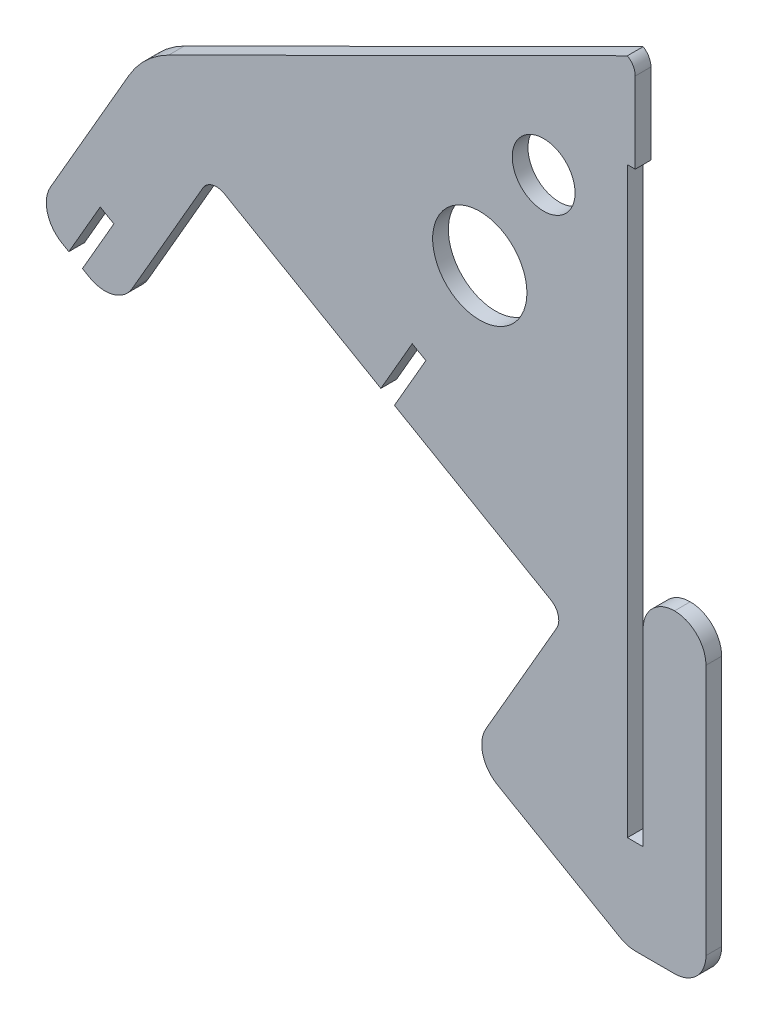
SolidWorks part; units mm, degrees
material "Oak"
ref_plane "Front Plane" through (0, 0, 0) normal (0, 0, 1) x (1, 0, 0)
ref_plane "Top Plane" through (0, 0, 0) normal (0, 1, 0) x (1, 0, 0)
ref_plane "Right Plane" through (0, 0, 0) normal (1, 0, 0) x (0, 0, -1)
sketch "Sketch1" plane through (0, 0, 0) normal (0, 0, 1) x (1, 0, 0)
  line L0 (19.8678, -317.9823) -> (-30.1322, -289.1148)
  line L1 (19.8678, -317.7572) -> (19.8678, -230.4572) construction
  line L2 (-30.1322, -289.1148) -> (-0.1322, -237.1533)
  line L3 (-0.1322, -237.1533) -> (-112.7155, -172.1533)
  line L4 (-112.7155, -172.1533) -> (-142.7155, -224.1148)
  line L5 (-142.7155, -224.1148) -> (-168.6963, -209.1148)
  line L6 (-168.6963, -209.1148) -> (-134.1825, -149.3352)
  line L7 (-134.1825, -149.3352) -> (19.8678, -72.5123)
  line L8 (19.8678, -130.2572) -> (19.8678, -42.9572) construction
  line L9 (19.8678, -72.5123) -> (19.8678, -287.9823)
  line L10 (19.8678, -317.9823) -> (44.8678, -317.9823)
  line L11 (44.8678, -317.9823) -> (44.8678, -217.9823)
  line L12 (44.8678, -217.9823) -> (24.8678, -217.9823)
  line L13 (24.8678, -217.9823) -> (24.8678, -287.9823)
  line L14 (24.8678, -317.7572) -> (24.8678, -230.4572) construction
  line L15 (24.8678, -287.9823) -> (19.8678, -287.9823)
  line L16 (24.8678, -230.4572) -> (24.8678, -130.2572) construction
  line L17 (-56.4239, -204.6533) -> (19.8678, -72.5123) construction
  line L18 (-58.589, -203.4033) -> (-48.589, -186.0828)
  line L19 (-48.589, -186.0828) -> (-44.2588, -188.5828)
  line L20 (-155.7059, -216.6148) -> (-145.7059, -199.2943) construction
  line L21 (-157.871, -215.3648) -> (-147.871, -198.0443)
  line L22 (-147.871, -198.0443) -> (-143.5409, -200.5443)
  line L23 (-153.5409, -217.8648) -> (-143.5409, -200.5443)
  line L24 (-54.2588, -205.9033) -> (-44.2588, -188.5828)
  line L25 (24.8678, -417.8572) -> (185.5376, -510.62) construction
  point P32 (-46.4239, -187.3328)
  dimension "D1" = 130
  dimension "D2" = 30
  dimension "D3" = 20
  dimension "D4" = 60
  dimension "D5" = 30
  dimension "D6" = 100
  dimension "D7" = 20
  dimension "D8" = 30
  dimension "D9" = 5
  dimension "D10" = 20
  dimension "D11" = 5
  dimension "D12" = 20
  dimension "D13" = 100
extrude "Boss-Extrude1" add sketch "Sketch1" along normal mid plane 5 contours L24 L3 L2 L0 L10 L11 L12 L13 L15 L9 L7 L6 L5 L21 L22 L23 L4 L18 L19 region at (-31.7791, -186.599, 0)
fillet "Fillet1" radius 10 7 edges at (-168.6963, -209.1148, 0) (-142.7155, -224.1148, 0) (-30.1322, -289.1148, 0) (19.8678, -317.9823, 0) (24.8678, -217.9823, 0) (44.8678, -217.9823, 0) (44.8678, -317.9823, 0)
sketch "Sketch2" plane through (0, 0, 2.5) normal (0, 0, 1) x (1, 0, 0)
  line L0 (19.8678, -72.5123) -> (22.3678, -72.5123)
  line L1 (22.3678, -72.5123) -> (22.3678, -102.5123)
  line L2 (22.3678, -102.5123) -> (19.8678, -102.5123)
  line L3 (19.8678, -72.5123) -> (19.8678, -287.9823) construction
  line L4 (19.8678, -72.5123) -> (19.8678, -102.5123)
  dimension "D1" = 2.5
  dimension "D2" = 30
extrude "Boss-Extrude2" add sketch "Sketch2" against normal blind 5
fillet "Fillet2" radius 5 1 edges at (22.3678, -72.5123, 0)
sketch "Sketch3" plane through (0, 0, 2.5) normal (0, 0, 1) x (1, 0, 0)
  line L0 (-46.4239, -187.3328) -> (19.8678, -72.5123) construction
  line L1 (-48.589, -186.0828) -> (-44.2588, -188.5828) construction
  circle A0 centre (-27.0976, -153.8587) radius 15
  circle A1 centre (-6.7753, -118.6594) radius 10
  dimension "D1" = 30
  dimension "D2" = 20
extrude "Cut-Extrude1" cut sketch "Sketch3" against normal blind 5
fillet "Fillet3" radius 30 1 edges at (-134.1825, -149.3352, 0)
fillet "Fillet4" radius 5 2 edges at (-112.7155, -172.1533, 0) (-0.1322, -237.1533, 0)
